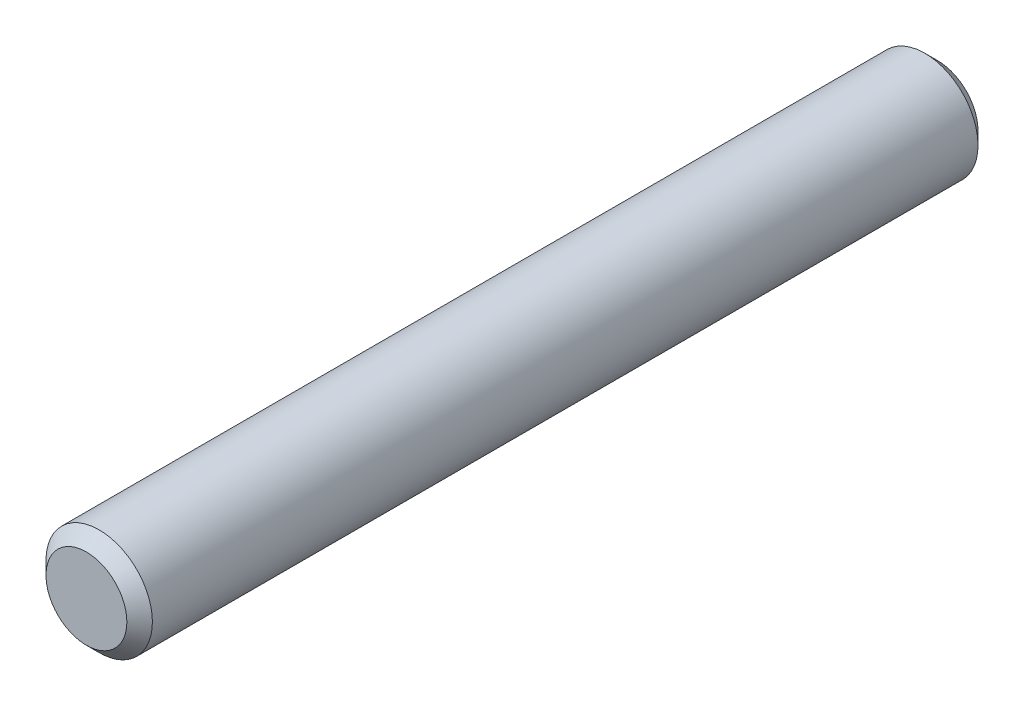
SolidWorks part; units mm, degrees
material "Temperguss"
ref_plane "Ebene vorne" through (0, 0, 0) normal (0, 0, 1) x (1, 0, 0)
ref_plane "Ebene oben" through (0, 0, 0) normal (0, 1, 0) x (1, 0, 0)
ref_plane "Ebene rechts" through (0, 0, 0) normal (1, 0, 0) x (0, 0, -1)
sketch "Skizze1" plane through (0, 0, 0) normal (0, 0, 1) x (1, 0, 0)
  circle A0 centre (-4.1799, 1.2472) radius 1.25
  dimension "D1" = 2.5
extrude "Aufsatz-Linear austragen1" add sketch "Skizze1" along normal blind 20
chamfer "Fase1" distance 0.3 angle 45 2 edges at (-2.9299, 1.2472, 20) (-2.9299, 1.2472, 0)
